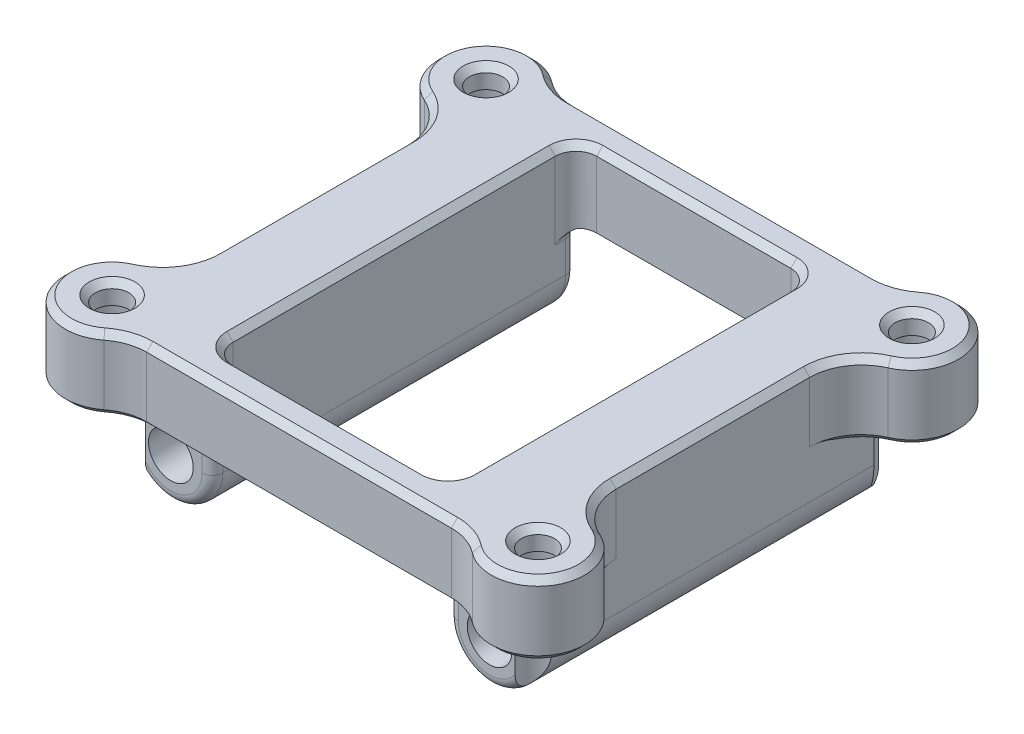
SolidWorks part; units mm, degrees
material "PLA"
ref_plane "正面" through (0, 0, 0) normal (0, 0, 1) x (1, 0, 0)
ref_plane "平面" through (0, 0, 0) normal (0, 1, 0) x (1, 0, 0)
ref_plane "右側面" through (0, 0, 0) normal (1, 0, 0) x (0, 0, -1)
sketch "ｽｹｯﾁ1" plane through (0, 0, 0) normal (0, 0, 1) x (1, 0, 0)
  line L0 (0, 0) -> (0, -9.0143) construction
  line L1 (0, 0) -> (35, 0) construction
  line L2 (0, 0) -> (15.343, 31.4578) construction
  line L3 (-7.343, 35.4578) -> (7.343, 35.4578)
  line L4 (-19.343, 31.4578) -> (-19.343, 35.4578)
  line L5 (-23.5, 42.4578) -> (23.5, 42.4578)
  line L6 (-23.5, 42.4578) -> (-23.5, 35.4578)
  line L7 (-23.5, 35.4578) -> (-23.343, 35.4578)
  line L8 (23.5, 42.4578) -> (23.5, 35.4578)
  line L9 (-23.5, 42.4578) -> (23.5, 35.4578) construction
  line L10 (-23.5, 35.4578) -> (23.5, 42.4578) construction
  line L11 (-15.343, 31.4578) -> (-15.343, 35.4578) construction
  line L12 (-23.343, 35.4578) -> (-15.343, 35.4578)
  line L13 (-7.343, 35.4578) -> (7.343, 35.4578)
  line L14 (-15.343, 35.4578) -> (-7.343, 35.4578)
  line L15 (-15.343, 35.4578) -> (-7.343, 35.4578) construction
  line L16 (7.343, 35.4578) -> (15.343, 35.4578)
  line L17 (23.343, 35.4578) -> (23.5, 35.4578)
  line L18 (7.343, 35.4578) -> (15.343, 35.4578) construction
  line L19 (15.343, 35.4578) -> (23.343, 35.4578)
  line L20 (-20.5, 42.4578) -> (-20.5, 35.4578) construction
  line L21 (20.5, 42.4578) -> (20.5, 35.4578) construction
  line L22 (-11.343, 31.4578) -> (-11.343, 35.4578)
  line L23 (11.343, 31.4578) -> (11.343, 35.4578)
  line L24 (19.343, 31.4578) -> (19.343, 35.4578)
  circle A2 centre (0, 0) radius 35 construction
  circle A4 centre (15.343, 31.4578) radius 2.15
  circle A5 centre (-15.343, 31.4578) radius 2.15
  arc A6 (11.6535, 33.003) -> (19.343, 31.4578) centre (15.343, 31.4578) ccw
  arc A7 (-11.6535, 33.003) -> (-19.343, 31.4578) centre (-15.343, 31.4578) cw
  arc A12 (-19.343, 31.4578) -> (-15.343, 35.4578) centre (-15.343, 31.4578) cw construction
  arc A13 (-15.343, 35.4578) -> (-11.6535, 33.003) centre (-15.343, 31.4578) cw construction
  arc A14 (15.343, 35.4578) -> (11.6535, 33.003) centre (15.343, 31.4578) ccw construction
  arc A15 (19.343, 31.4578) -> (15.343, 35.4578) centre (15.343, 31.4578) ccw construction
  point P15 (0, 38.9578)
  dimension "D1" = 70
  dimension "D2" = 64
  dimension "D3" = 4.3
  dimension "D4" = 8
  dimension "D5" = 47
  dimension "D6" = 7
  dimension "D7" = 41
extrude "ﾎﾞｽ - 押し出し1" add sketch "ｽｹｯﾁ1" along normal blind 42 contours L17 L8 L5 L6 L7 A7 L3 A6 A4 A5 | A7 L22 L14 L12 L4 A5 | L23 A6 L24 L19 L16 A4 region at (0, 38.9578, 0) region at (-11.4561, 33.4578, 0) region at (13.343, 35.3447, 0)
sketch "ｽｹｯﾁ2" plane through (0, 42.4578, 0) normal (0, 1, 0) x (1, 0, 0)
  line L0 (0, 0) -> (0, -42) construction
  line L1 (-23.5, -42) -> (23.5, -42) construction
  line L2 (0, -21) -> (20.5, -21) construction
  line L3 (-20.5, -3) -> (20.5, -3) construction
  line L4 (-20.5, -3) -> (-20.5, -39) construction
  line L5 (-20.5, -39) -> (20.5, -39) construction
  line L6 (20.5, -3) -> (20.5, -39) construction
  line L7 (-20.5, -3) -> (20.5, -39) construction
  line L8 (-20.5, -39) -> (20.5, -3) construction
  circle A0 centre (20.5, -3) radius 1.6
  circle A1 centre (-20.5, -3) radius 1.6
  circle A2 centre (20.5, -39) radius 1.6
  circle A3 centre (-20.5, -39) radius 1.6
  point P5 (0, -21)
  dimension "D3" = 3.2
  dimension "D1" = 41
  dimension "D2" = 36
extrude "ｶｯﾄ - 押し出し2" cut sketch "ｽｹｯﾁ2" against normal blind 7
sketch "ｽｹｯﾁ4" plane through (0, 0, 42) normal (0, 0, 1) x (1, 0, 0)
  line L0 (-19.343, 35.4578) -> (19.343, 35.4578)
  line L10 (-23.5, 35.4578) -> (-19.343, 35.4578)
  line L11 (-19.343, 35.4578) -> (-19.343, 31.4578)
  line L12 (-11.343, 31.4578) -> (-11.343, 35.4578)
  line L13 (-11.343, 35.4578) -> (11.343, 35.4578)
  line L14 (11.343, 35.4578) -> (11.343, 31.4578)
  line L15 (19.343, 31.4578) -> (19.343, 35.4578)
  line L16 (-23.5, 35.4578) -> (-19.343, 35.4578)
  line L17 (23.5, 35.4578) -> (23.5, 42.4578)
  line L18 (23.5, 42.4578) -> (-23.5, 42.4578)
  line L19 (-23.5, 42.4578) -> (-23.5, 35.4578)
  line L21 (-19.343, 35.4578) -> (-19.343, 31.4578)
  line L22 (-11.343, 31.4578) -> (-11.343, 35.4578)
  line L23 (-11.343, 35.4578) -> (11.343, 35.4578)
  line L24 (11.343, 35.4578) -> (11.343, 31.4578)
  line L25 (19.343, 31.4578) -> (19.343, 35.4578)
  line L27 (23.5, 35.4578) -> (23.5, 42.4578)
  line L28 (23.5, 42.4578) -> (-23.5, 42.4578)
  line L29 (-23.5, 42.4578) -> (-23.5, 35.4578)
  line L31 (19.343, 35.4578) -> (23.5, 35.4578)
  line L32 (19.343, 35.4578) -> (23.5, 35.4578)
  arc A2 (-19.343, 31.4578) -> (-11.343, 31.4578) centre (-15.343, 31.4578) ccw
  arc A3 (11.343, 31.4578) -> (19.343, 31.4578) centre (15.343, 31.4578) ccw
  arc A4 (-19.343, 31.4578) -> (-11.343, 31.4578) centre (-15.343, 31.4578) ccw
  arc A5 (11.343, 31.4578) -> (19.343, 31.4578) centre (15.343, 31.4578) ccw
  line M14 (-19.343, 35.4578) -> (-19.343, 31.4578)
  arc M15 (-19.343, 31.4578) -> (-11.343, 31.4578) centre (-15.343, 31.4578) ccw
  line M16 (-11.343, 31.4578) -> (-11.343, 35.4578)
  line M18 (11.343, 35.4578) -> (11.343, 31.4578)
  arc M19 (11.343, 31.4578) -> (19.343, 31.4578) centre (15.343, 31.4578) ccw
  line M20 (19.343, 31.4578) -> (19.343, 35.4578)
  circle M25 centre (15.343, 31.4578) radius 2.15
  circle M26 centre (-15.343, 31.4578) radius 2.15
  dimension "D1" = 0
extrude "ｶｯﾄ - 押し出し3" cut sketch "ｽｹｯﾁ4" against normal blind 3.5 contours L0 M18 M19 M20 M25 | L0 M14 M15 M16 M26 region at (-15.343, 35.3447, 42) region at (15.343, 35.3447, 42)
sketch "ｽｹｯﾁ5" plane through (0, 0, 0) normal (0, 0, -1) x (-1, 0, 0)
  line L0 (-19.343, 35.4578) -> (19.343, 35.4578)
  line L10 (19.343, 35.4578) -> (23.5, 35.4578)
  line L11 (23.5, 35.4578) -> (23.5, 42.4578)
  line L12 (23.5, 42.4578) -> (-23.5, 42.4578)
  line L13 (-23.5, 42.4578) -> (-23.5, 35.4578)
  line L14 (19.343, 35.4578) -> (23.5, 35.4578)
  line L15 (-19.343, 35.4578) -> (-19.343, 31.4578)
  line L16 (-11.343, 31.4578) -> (-11.343, 35.4578)
  line L17 (-23.5, 35.4578) -> (-19.343, 35.4578)
  line L18 (11.343, 35.4578) -> (11.343, 31.4578)
  line L19 (19.343, 31.4578) -> (19.343, 35.4578)
  line L21 (23.5, 35.4578) -> (23.5, 42.4578)
  line L22 (23.5, 42.4578) -> (-23.5, 42.4578)
  line L23 (-23.5, 42.4578) -> (-23.5, 35.4578)
  line L25 (-19.343, 35.4578) -> (-19.343, 31.4578)
  line L26 (-11.343, 31.4578) -> (-11.343, 35.4578)
  line L28 (11.343, 35.4578) -> (11.343, 31.4578)
  line L29 (19.343, 31.4578) -> (19.343, 35.4578)
  line L31 (-23.5, 35.4578) -> (-19.343, 35.4578)
  line L32 (-11.343, 35.4578) -> (11.343, 35.4578)
  line L33 (-11.343, 35.4578) -> (11.343, 35.4578)
  arc A2 (-19.343, 31.4578) -> (-11.343, 31.4578) centre (-15.343, 31.4578) ccw
  arc A3 (11.343, 31.4578) -> (19.343, 31.4578) centre (15.343, 31.4578) ccw
  arc A4 (-19.343, 31.4578) -> (-11.343, 31.4578) centre (-15.343, 31.4578) ccw
  arc A5 (11.343, 31.4578) -> (19.343, 31.4578) centre (15.343, 31.4578) ccw
  line M18 (-19.343, 35.4578) -> (-19.343, 31.4578)
  arc M19 (-19.343, 31.4578) -> (-11.343, 31.4578) centre (-15.343, 31.4578) ccw
  line M20 (-11.343, 31.4578) -> (-11.343, 35.4578)
  line M22 (11.343, 35.4578) -> (11.343, 31.4578)
  arc M23 (11.343, 31.4578) -> (19.343, 31.4578) centre (15.343, 31.4578) ccw
  line M24 (19.343, 31.4578) -> (19.343, 35.4578)
  circle M25 centre (-15.343, 31.4578) radius 2.15
  circle M26 centre (15.343, 31.4578) radius 2.15
  dimension "D1" = 0
extrude "ｶｯﾄ - 押し出し4" cut sketch "ｽｹｯﾁ5" against normal blind 3.5 contours L0 M22 M23 M24 M26 | L0 M18 M19 M20 M25 region at (15.343, 35.3447, 0) region at (-15.343, 35.3447, 0)
sketch "ｽｹｯﾁ7" plane through (0, 42.4578, 0) normal (0, 1, 0) x (1, 0, 0)
  line L0 (0, 0) -> (0, -42) construction
  line L1 (-23.5, -42) -> (23.5, -42) construction
  line L2 (23.5, -21) -> (0, -21) construction
  line L3 (23.5, -42) -> (23.5, 0) construction
  circle A0 centre (20.5, -3) radius 4.5
  circle A1 centre (20.5, -39) radius 4.5
  circle A2 centre (20.5, -39) radius 4.5
  circle A3 centre (20.5, -3) radius 4.5
  circle A4 centre (-20.5, -39) radius 4.5
  circle A5 centre (-20.5, -3) radius 4.5
  line M8 (23.5, 0) -> (-23.5, 0)
  line M9 (-23.5, 0) -> (-23.5, -42)
  line M10 (-23.5, -42) -> (23.5, -42)
  line M11 (23.5, -42) -> (23.5, 0)
  dimension "D1" = 9
extrude "ﾎﾞｽ - 押し出し2" add sketch "ｽｹｯﾁ7" against normal blind 7 contours A5 M9 M8 | A0 M11 M8 | A1 M11 M10 | A4 M9 M10 region at (24.5065, 42.4578, 4.7918) region at (-20.3229, 42.4578, -0.1111) region at (24.5065, 42.4578, 37.2082) region at (-23.6111, 42.4578, 38.8229)
sketch "ｽｹｯﾁ10" plane through (0, 35.4578, 0) normal (0, -1, 0) x (1, 0, 0)
  line L0 (0, 0) -> (0, 42) construction
  line L1 (-17.1459, 42) -> (17.1459, 42) construction
  line L2 (0, 21) -> (23.5, 21) construction
  line L3 (23.5, 35.6459) -> (23.5, 6.3541) construction
  circle A0 centre (20.5, 39) radius 2.6
  circle A1 centre (20.5, 3) radius 2.6
  circle A2 centre (-20.5, 39) radius 2.6
  circle A3 centre (-20.5, 3) radius 2.6
  dimension "D1" = 5.2
extrude "ｶｯﾄ - 押し出し7" cut sketch "ｽｹｯﾁ10" against normal blind 5
sketch "ｽｹｯﾁ8" plane through (0, 35.4578, 0) normal (0, -1, 0) x (1, 0, 0)
  line L0 (19.5566, 41.5) -> (19.0566, 41.5) construction
  line L1 (22.1934, 36.933) -> (23.1368, 38.567)
  line L2 (23.1368, 39.433) -> (22.1934, 41.067)
  line L3 (21.4434, 41.5) -> (19.5566, 41.5)
  line L4 (18.8066, 41.067) -> (17.8632, 39.433)
  line L5 (17.8632, 38.567) -> (18.8066, 36.933)
  line L6 (19.5566, 36.5) -> (21.4434, 36.5)
  line L7 (19.0566, 41.5) -> (18.8066, 41.067) construction
  line L8 (21.9434, 41.5) -> (21.4434, 41.5) construction
  line L9 (22.1934, 41.067) -> (21.9434, 41.5) construction
  line L10 (23.3868, 39) -> (23.1368, 39.433) construction
  line L11 (23.1368, 38.567) -> (23.3868, 39) construction
  line L12 (21.9434, 36.5) -> (22.1934, 36.933) construction
  line L13 (21.4434, 36.5) -> (21.9434, 36.5) construction
  line L14 (18.8066, 36.933) -> (19.0566, 36.5) construction
  line L15 (19.0566, 36.5) -> (19.5566, 36.5) construction
  line L16 (17.8632, 39.433) -> (17.6132, 39) construction
  line L17 (17.6132, 39) -> (17.8632, 38.567) construction
  line L18 (0, 0) -> (0, 42) construction
  line L19 (-17.1459, 42) -> (17.1459, 42) construction
  line L20 (0, 21) -> (23.5, 21) construction
  line L21 (23.5, 35.6459) -> (23.5, 6.3541) construction
  line L22 (-17.6132, 39) -> (-17.8632, 38.567) construction
  line L23 (-17.8632, 39.433) -> (-17.6132, 39) construction
  line L24 (-19.0566, 36.5) -> (-19.5566, 36.5) construction
  line L25 (-18.8066, 36.933) -> (-19.0566, 36.5) construction
  line L26 (-21.4434, 36.5) -> (-21.9434, 36.5) construction
  line L27 (-21.9434, 36.5) -> (-22.1934, 36.933) construction
  line L28 (-22.1934, 41.067) -> (-21.9434, 41.5) construction
  line L29 (-21.9434, 41.5) -> (-21.4434, 41.5) construction
  line L30 (-19.0566, 41.5) -> (-18.8066, 41.067) construction
  line L31 (-19.5566, 41.5) -> (-19.0566, 41.5) construction
  line L32 (-19.5566, 36.5) -> (-21.4434, 36.5)
  line L33 (-17.8632, 38.567) -> (-18.8066, 36.933)
  line L34 (-18.8066, 41.067) -> (-17.8632, 39.433)
  line L35 (-21.4434, 41.5) -> (-19.5566, 41.5)
  line L36 (-23.1368, 39.433) -> (-22.1934, 41.067)
  line L37 (-22.1934, 36.933) -> (-23.1368, 38.567)
  line L38 (17.6132, 3) -> (17.8632, 3.433) construction
  line L39 (17.8632, 2.567) -> (17.6132, 3) construction
  line L40 (19.0566, 5.5) -> (19.5566, 5.5) construction
  line L41 (18.8066, 5.067) -> (19.0566, 5.5) construction
  line L42 (21.4434, 5.5) -> (21.9434, 5.5) construction
  line L43 (21.9434, 5.5) -> (22.1934, 5.067) construction
  line L44 (23.1368, 3.433) -> (23.3868, 3) construction
  line L45 (23.3868, 3) -> (23.1368, 2.567) construction
  line L46 (22.1934, 0.933) -> (21.9434, 0.5) construction
  line L47 (21.9434, 0.5) -> (21.4434, 0.5) construction
  line L48 (19.0566, 0.5) -> (18.8066, 0.933) construction
  line L49 (19.5566, 0.5) -> (19.0566, 0.5) construction
  line L50 (19.5566, 5.5) -> (21.4434, 5.5)
  line L51 (17.8632, 3.433) -> (18.8066, 5.067)
  line L52 (18.8066, 0.933) -> (17.8632, 2.567)
  line L53 (21.4434, 0.5) -> (19.5566, 0.5)
  line L54 (23.1368, 2.567) -> (22.1934, 0.933)
  line L55 (22.1934, 5.067) -> (23.1368, 3.433)
  line L56 (-19.5566, 0.5) -> (-19.0566, 0.5) construction
  line L57 (-19.0566, 0.5) -> (-18.8066, 0.933) construction
  line L58 (-21.9434, 0.5) -> (-21.4434, 0.5) construction
  line L59 (-22.1934, 0.933) -> (-21.9434, 0.5) construction
  line L60 (-23.3868, 3) -> (-23.1368, 2.567) construction
  line L61 (-23.1368, 3.433) -> (-23.3868, 3) construction
  line L62 (-21.9434, 5.5) -> (-22.1934, 5.067) construction
  line L63 (-21.4434, 5.5) -> (-21.9434, 5.5) construction
  line L64 (-18.8066, 5.067) -> (-19.0566, 5.5) construction
  line L65 (-19.0566, 5.5) -> (-19.5566, 5.5) construction
  line L66 (-17.8632, 2.567) -> (-17.6132, 3) construction
  line L67 (-17.6132, 3) -> (-17.8632, 3.433) construction
  line L68 (-22.1934, 5.067) -> (-23.1368, 3.433)
  line L69 (-23.1368, 2.567) -> (-22.1934, 0.933)
  line L70 (-21.4434, 0.5) -> (-19.5566, 0.5)
  line L71 (-18.8066, 0.933) -> (-17.8632, 2.567)
  line L72 (-17.8632, 3.433) -> (-18.8066, 5.067)
  line L73 (-19.5566, 5.5) -> (-21.4434, 5.5)
  arc A0 (22.9826, 39.2944) -> (18.0174, 39.2944) centre (20.5, 39) ccw construction
  arc A1 (21.4864, 41.2972) -> (21.9963, 41.0028) centre (21.9434, 41.5) ccw construction
  arc A2 (23.1368, 38.567) -> (23.1368, 39.433) centre (23.3868, 39) ccw
  arc A3 (21.4434, 36.5) -> (22.1934, 36.933) centre (21.9434, 36.5) ccw
  arc A4 (18.8066, 36.933) -> (19.5566, 36.5) centre (19.0566, 36.5) ccw
  arc A5 (17.8632, 39.433) -> (17.8632, 38.567) centre (17.6132, 39) ccw
  arc A6 (19.5566, 41.5) -> (18.8066, 41.067) centre (19.0566, 41.5) ccw
  arc A7 (18.8066, 41.067) -> (19.0037, 41.0028) centre (19.0566, 41.5) ccw construction
  arc A8 (19.0037, 41.0028) -> (19.5136, 41.2972) centre (19.0566, 41.5) ccw construction
  arc A9 (19.5136, 41.2972) -> (19.5566, 41.5) centre (19.0566, 41.5) ccw construction
  arc A10 (21.4434, 41.5) -> (21.4864, 41.2972) centre (21.9434, 41.5) ccw construction
  arc A11 (21.9963, 41.0028) -> (22.1934, 41.067) centre (21.9434, 41.5) ccw construction
  arc A12 (22.1934, 41.067) -> (21.4434, 41.5) centre (21.9434, 41.5) ccw
  arc A13 (23.1368, 39.433) -> (22.9826, 39.2944) centre (23.3868, 39) ccw construction
  arc A14 (22.9826, 38.7056) -> (22.9826, 39.2944) centre (20.5, 39) ccw construction
  arc A15 (22.9826, 39.2944) -> (22.9826, 38.7056) centre (23.3868, 39) ccw construction
  arc A16 (22.9826, 38.7056) -> (23.1368, 38.567) centre (23.3868, 39) ccw construction
  arc A17 (22.1934, 36.933) -> (21.9963, 36.9972) centre (21.9434, 36.5) ccw construction
  arc A18 (21.9963, 36.9972) -> (22.6651, 37.75) centre (20.5, 39) ccw construction
  arc A19 (22.6651, 37.75) -> (22.9826, 38.7056) centre (20.5, 39) ccw construction
  arc A20 (21.9963, 36.9972) -> (21.4864, 36.7028) centre (21.9434, 36.5) ccw construction
  arc A21 (21.4864, 36.7028) -> (21.9963, 36.9972) centre (20.5, 39) ccw construction
  arc A22 (21.4864, 36.7028) -> (21.4434, 36.5) centre (21.9434, 36.5) ccw construction
  arc A23 (19.0037, 36.9972) -> (18.8066, 36.933) centre (19.0566, 36.5) ccw construction
  arc A24 (18.3349, 37.75) -> (19.0037, 36.9972) centre (20.5, 39) ccw construction
  arc A25 (19.5136, 36.7028) -> (21.4864, 36.7028) centre (20.5, 39) ccw construction
  arc A26 (19.5136, 36.7028) -> (19.0037, 36.9972) centre (19.0566, 36.5) ccw construction
  arc A27 (19.0037, 36.9972) -> (19.5136, 36.7028) centre (20.5, 39) ccw construction
  arc A28 (19.5566, 36.5) -> (19.5136, 36.7028) centre (19.0566, 36.5) ccw construction
  arc A29 (18.0174, 39.2944) -> (18.0174, 38.7056) centre (20.5, 39) ccw construction
  arc A30 (18.0174, 38.7056) -> (18.3349, 37.75) centre (20.5, 39) ccw construction
  arc A31 (18.0174, 38.7056) -> (18.0174, 39.2944) centre (17.6132, 39) ccw construction
  arc A32 (18.0174, 39.2944) -> (17.8632, 39.433) centre (17.6132, 39) ccw construction
  arc A33 (17.8632, 38.567) -> (18.0174, 38.7056) centre (17.6132, 39) ccw construction
  arc A34 (-23.1368, 38.567) -> (-23.1368, 39.433) centre (-23.3868, 39) cw
  arc A35 (-17.8632, 38.567) -> (-18.0174, 38.7056) centre (-17.6132, 39) cw construction
  arc A36 (-18.0174, 39.2944) -> (-17.8632, 39.433) centre (-17.6132, 39) cw construction
  arc A37 (-18.0174, 38.7056) -> (-18.0174, 39.2944) centre (-17.6132, 39) cw construction
  arc A38 (-18.0174, 38.7056) -> (-18.3349, 37.75) centre (-20.5, 39) cw construction
  arc A39 (-18.0174, 39.2944) -> (-18.0174, 38.7056) centre (-20.5, 39) cw construction
  arc A40 (-19.5566, 36.5) -> (-19.5136, 36.7028) centre (-19.0566, 36.5) cw construction
  arc A41 (-19.0037, 36.9972) -> (-19.5136, 36.7028) centre (-20.5, 39) cw construction
  arc A42 (-19.5136, 36.7028) -> (-19.0037, 36.9972) centre (-19.0566, 36.5) cw construction
  arc A43 (-19.5136, 36.7028) -> (-21.4864, 36.7028) centre (-20.5, 39) cw construction
  arc A44 (-18.3349, 37.75) -> (-19.0037, 36.9972) centre (-20.5, 39) cw construction
  arc A45 (-19.0037, 36.9972) -> (-18.8066, 36.933) centre (-19.0566, 36.5) cw construction
  arc A46 (-21.4864, 36.7028) -> (-21.4434, 36.5) centre (-21.9434, 36.5) cw construction
  arc A47 (-21.4864, 36.7028) -> (-21.9963, 36.9972) centre (-20.5, 39) cw construction
  arc A48 (-21.9963, 36.9972) -> (-21.4864, 36.7028) centre (-21.9434, 36.5) cw construction
  arc A49 (-22.6651, 37.75) -> (-22.9826, 38.7056) centre (-20.5, 39) cw construction
  arc A50 (-21.9963, 36.9972) -> (-22.6651, 37.75) centre (-20.5, 39) cw construction
  arc A51 (-22.1934, 36.933) -> (-21.9963, 36.9972) centre (-21.9434, 36.5) cw construction
  arc A52 (-22.9826, 38.7056) -> (-23.1368, 38.567) centre (-23.3868, 39) cw construction
  arc A53 (-22.9826, 39.2944) -> (-22.9826, 38.7056) centre (-23.3868, 39) cw construction
  arc A54 (-22.9826, 38.7056) -> (-22.9826, 39.2944) centre (-20.5, 39) cw construction
  arc A55 (-23.1368, 39.433) -> (-22.9826, 39.2944) centre (-23.3868, 39) cw construction
  arc A56 (-21.9963, 41.0028) -> (-22.1934, 41.067) centre (-21.9434, 41.5) cw construction
  arc A57 (-21.4434, 41.5) -> (-21.4864, 41.2972) centre (-21.9434, 41.5) cw construction
  arc A58 (-19.5136, 41.2972) -> (-19.5566, 41.5) centre (-19.0566, 41.5) cw construction
  arc A59 (-19.0037, 41.0028) -> (-19.5136, 41.2972) centre (-19.0566, 41.5) cw construction
  arc A60 (-18.8066, 41.067) -> (-19.0037, 41.0028) centre (-19.0566, 41.5) cw construction
  arc A61 (-21.4864, 41.2972) -> (-21.9963, 41.0028) centre (-21.9434, 41.5) cw construction
  arc A62 (-22.9826, 39.2944) -> (-18.0174, 39.2944) centre (-20.5, 39) cw construction
  arc A63 (-22.1934, 41.067) -> (-21.4434, 41.5) centre (-21.9434, 41.5) cw
  arc A64 (-19.5566, 41.5) -> (-18.8066, 41.067) centre (-19.0566, 41.5) cw
  arc A65 (-17.8632, 39.433) -> (-17.8632, 38.567) centre (-17.6132, 39) cw
  arc A66 (-18.8066, 36.933) -> (-19.5566, 36.5) centre (-19.0566, 36.5) cw
  arc A67 (-21.4434, 36.5) -> (-22.1934, 36.933) centre (-21.9434, 36.5) cw
  arc A68 (23.1368, 3.433) -> (23.1368, 2.567) centre (23.3868, 3) cw
  arc A69 (17.8632, 3.433) -> (18.0174, 3.2944) centre (17.6132, 3) cw construction
  arc A70 (18.0174, 2.7056) -> (17.8632, 2.567) centre (17.6132, 3) cw construction
  arc A71 (18.0174, 3.2944) -> (18.0174, 2.7056) centre (17.6132, 3) cw construction
  arc A72 (18.0174, 3.2944) -> (18.3349, 4.25) centre (20.5, 3) cw construction
  arc A73 (18.0174, 2.7056) -> (18.0174, 3.2944) centre (20.5, 3) cw construction
  arc A74 (19.5566, 5.5) -> (19.5136, 5.2972) centre (19.0566, 5.5) cw construction
  arc A75 (19.0037, 5.0028) -> (19.5136, 5.2972) centre (20.5, 3) cw construction
  arc A76 (19.5136, 5.2972) -> (19.0037, 5.0028) centre (19.0566, 5.5) cw construction
  arc A77 (19.5136, 5.2972) -> (21.4864, 5.2972) centre (20.5, 3) cw construction
  arc A78 (18.3349, 4.25) -> (19.0037, 5.0028) centre (20.5, 3) cw construction
  arc A79 (19.0037, 5.0028) -> (18.8066, 5.067) centre (19.0566, 5.5) cw construction
  arc A80 (21.4864, 5.2972) -> (21.4434, 5.5) centre (21.9434, 5.5) cw construction
  arc A81 (21.4864, 5.2972) -> (21.9963, 5.0028) centre (20.5, 3) cw construction
  arc A82 (21.9963, 5.0028) -> (21.4864, 5.2972) centre (21.9434, 5.5) cw construction
  arc A83 (22.6651, 4.25) -> (22.9826, 3.2944) centre (20.5, 3) cw construction
  arc A84 (21.9963, 5.0028) -> (22.6651, 4.25) centre (20.5, 3) cw construction
  arc A85 (22.1934, 5.067) -> (21.9963, 5.0028) centre (21.9434, 5.5) cw construction
  arc A86 (22.9826, 3.2944) -> (23.1368, 3.433) centre (23.3868, 3) cw construction
  arc A87 (22.9826, 2.7056) -> (22.9826, 3.2944) centre (23.3868, 3) cw construction
  arc A88 (22.9826, 3.2944) -> (22.9826, 2.7056) centre (20.5, 3) cw construction
  arc A89 (23.1368, 2.567) -> (22.9826, 2.7056) centre (23.3868, 3) cw construction
  arc A90 (21.9963, 0.9972) -> (22.1934, 0.933) centre (21.9434, 0.5) cw construction
  arc A91 (21.4434, 0.5) -> (21.4864, 0.7028) centre (21.9434, 0.5) cw construction
  arc A92 (19.5136, 0.7028) -> (19.5566, 0.5) centre (19.0566, 0.5) cw construction
  arc A93 (19.0037, 0.9972) -> (19.5136, 0.7028) centre (19.0566, 0.5) cw construction
  arc A94 (18.8066, 0.933) -> (19.0037, 0.9972) centre (19.0566, 0.5) cw construction
  arc A95 (21.4864, 0.7028) -> (21.9963, 0.9972) centre (21.9434, 0.5) cw construction
  arc A96 (22.9826, 2.7056) -> (18.0174, 2.7056) centre (20.5, 3) cw construction
  arc A97 (22.1934, 0.933) -> (21.4434, 0.5) centre (21.9434, 0.5) cw
  arc A98 (19.5566, 0.5) -> (18.8066, 0.933) centre (19.0566, 0.5) cw
  arc A99 (17.8632, 2.567) -> (17.8632, 3.433) centre (17.6132, 3) cw
  arc A100 (18.8066, 5.067) -> (19.5566, 5.5) centre (19.0566, 5.5) cw
  arc A101 (21.4434, 5.5) -> (22.1934, 5.067) centre (21.9434, 5.5) cw
  arc A102 (-22.9826, 2.7056) -> (-18.0174, 2.7056) centre (-20.5, 3) ccw construction
  arc A103 (-21.4864, 0.7028) -> (-21.9963, 0.9972) centre (-21.9434, 0.5) ccw construction
  arc A104 (-18.8066, 0.933) -> (-19.0037, 0.9972) centre (-19.0566, 0.5) ccw construction
  arc A105 (-19.0037, 0.9972) -> (-19.5136, 0.7028) centre (-19.0566, 0.5) ccw construction
  arc A106 (-19.5136, 0.7028) -> (-19.5566, 0.5) centre (-19.0566, 0.5) ccw construction
  arc A107 (-21.4434, 0.5) -> (-21.4864, 0.7028) centre (-21.9434, 0.5) ccw construction
  arc A108 (-21.9963, 0.9972) -> (-22.1934, 0.933) centre (-21.9434, 0.5) ccw construction
  arc A109 (-23.1368, 2.567) -> (-22.9826, 2.7056) centre (-23.3868, 3) ccw construction
  arc A110 (-22.9826, 3.2944) -> (-22.9826, 2.7056) centre (-20.5, 3) ccw construction
  arc A111 (-22.9826, 2.7056) -> (-22.9826, 3.2944) centre (-23.3868, 3) ccw construction
  arc A112 (-22.9826, 3.2944) -> (-23.1368, 3.433) centre (-23.3868, 3) ccw construction
  arc A113 (-22.1934, 5.067) -> (-21.9963, 5.0028) centre (-21.9434, 5.5) ccw construction
  arc A114 (-21.9963, 5.0028) -> (-22.6651, 4.25) centre (-20.5, 3) ccw construction
  arc A115 (-22.6651, 4.25) -> (-22.9826, 3.2944) centre (-20.5, 3) ccw construction
  arc A116 (-21.9963, 5.0028) -> (-21.4864, 5.2972) centre (-21.9434, 5.5) ccw construction
  arc A117 (-21.4864, 5.2972) -> (-21.9963, 5.0028) centre (-20.5, 3) ccw construction
  arc A118 (-21.4864, 5.2972) -> (-21.4434, 5.5) centre (-21.9434, 5.5) ccw construction
  arc A119 (-19.0037, 5.0028) -> (-18.8066, 5.067) centre (-19.0566, 5.5) ccw construction
  arc A120 (-18.3349, 4.25) -> (-19.0037, 5.0028) centre (-20.5, 3) ccw construction
  arc A121 (-19.5136, 5.2972) -> (-21.4864, 5.2972) centre (-20.5, 3) ccw construction
  arc A122 (-19.5136, 5.2972) -> (-19.0037, 5.0028) centre (-19.0566, 5.5) ccw construction
  arc A123 (-19.0037, 5.0028) -> (-19.5136, 5.2972) centre (-20.5, 3) ccw construction
  arc A124 (-19.5566, 5.5) -> (-19.5136, 5.2972) centre (-19.0566, 5.5) ccw construction
  arc A125 (-18.0174, 2.7056) -> (-18.0174, 3.2944) centre (-20.5, 3) ccw construction
  arc A126 (-18.0174, 3.2944) -> (-18.3349, 4.25) centre (-20.5, 3) ccw construction
  arc A127 (-18.0174, 3.2944) -> (-18.0174, 2.7056) centre (-17.6132, 3) ccw construction
  arc A128 (-18.0174, 2.7056) -> (-17.8632, 2.567) centre (-17.6132, 3) ccw construction
  arc A129 (-17.8632, 3.433) -> (-18.0174, 3.2944) centre (-17.6132, 3) ccw construction
  arc A130 (-21.4434, 5.5) -> (-22.1934, 5.067) centre (-21.9434, 5.5) ccw
  arc A131 (-18.8066, 5.067) -> (-19.5566, 5.5) centre (-19.0566, 5.5) ccw
  arc A132 (-17.8632, 2.567) -> (-17.8632, 3.433) centre (-17.6132, 3) ccw
  arc A133 (-19.5566, 0.5) -> (-18.8066, 0.933) centre (-19.0566, 0.5) ccw
  arc A134 (-22.1934, 0.933) -> (-21.4434, 0.5) centre (-21.9434, 0.5) ccw
  arc A135 (-23.1368, 3.433) -> (-23.1368, 2.567) centre (-23.3868, 3) ccw
  dimension "D2" = 1
  dimension "D1" = 5
  dimension "D3" = 6
extrude "ｶｯﾄ - 押し出し5" [suppressed] cut sketch "ｽｹｯﾁ8" against normal blind 3
sketch "ｽｹｯﾁ11" plane through (0, 35.4578, 0) normal (0, -1, 0) x (1, 0, 0)
  line L0 (0, 42) -> (0, 0) construction
  line L1 (-17.1459, 42) -> (17.1459, 42) construction
  line L2 (0, 21) -> (23.5, 21) construction
  line L3 (23.5, 35.6459) -> (23.5, 6.3541) construction
  circle A0 centre (20.5, 39) radius 2.75
  circle A1 centre (20.5, 3) radius 2.75
  circle A2 centre (-20.5, 39) radius 2.75
  circle A3 centre (-20.5, 3) radius 2.75
  dimension "D1" = 5.5
extrude "ｶｯﾄ - 押し出し8" cut sketch "ｽｹｯﾁ11" along normal through all
sketch "ｽｹｯﾁ12" plane through (0, 42.4578, 0) normal (0, 1, 0) x (1, 0, 0)
  line L0 (0, 0) -> (0, -42) construction
  line L1 (-17.1459, -42) -> (17.1459, -42) construction
  line L2 (0, -21) -> (23.5, -21) construction
  line L3 (-16.7583, -0.5) -> (16.7583, -0.5)
  line L4 (-17.1459, -0.5) -> (-17.1459, 0) construction
  line L5 (-17.1459, 0) -> (17.1459, 0)
  line L6 (17.1459, -0.5) -> (17.1459, 0) construction
  line L7 (-16.7621, -0.4944) -> (17.1459, 0) construction
  line L8 (-17.1459, 0) -> (16.7621, -0.4944) construction
  line L9 (23.5, -35.6459) -> (23.5, -6.3541) construction
  line L10 (-17.1459, -42) -> (16.7621, -41.5056) construction
  line L11 (-16.7621, -41.5056) -> (17.1459, -42) construction
  line L12 (17.1459, -41.5) -> (17.1459, -42) construction
  line L13 (-17.1459, -42) -> (17.1459, -42)
  line L14 (-17.1459, -41.5) -> (-17.1459, -42) construction
  line L15 (-16.7583, -41.5) -> (16.7583, -41.5)
  line L16 (16.7621, -0.4944) -> (17.1459, -0.5) construction
  line L17 (16.7583, -0.5) -> (17.1459, -0.5) construction
  line L18 (23.5, -21) -> (23.5, -6.3541) construction
  line L19 (16.7621, -41.5056) -> (17.1459, -41.5) construction
  line L20 (-23.5, -6.3541) -> (-23.5, -35.6459)
  line L21 (-23.5, -6.3541) -> (-23.5, -35.6459)
  line L22 (-17.1459, -42) -> (17.1459, -42)
  line L23 (-17.1459, -42) -> (17.1459, -42)
  line L24 (23.5, -35.6459) -> (23.5, -6.3541)
  line L25 (23.5, -35.6459) -> (23.5, -6.3541)
  line L26 (17.1459, 0) -> (-17.1459, 0)
  line L27 (17.1459, 0) -> (-17.1459, 0)
  line L28 (16.7583, -41.5) -> (17.1459, -41.5) construction
  line L29 (-17.1459, -41.5) -> (-16.7583, -41.5) construction
  line L30 (-17.1459, -41.5) -> (-16.7621, -41.5056) construction
  line L31 (-17.1459, -0.5) -> (-16.7621, -0.4944) construction
  line L32 (-17.1459, -0.5) -> (-16.7583, -0.5) construction
  arc A0 (17.1459, 0) -> (16.7583, -0.5) centre (20.5, -3) ccw
  arc A1 (17.1459, -42) -> (16.7583, -41.5) centre (20.5, -39) cw
  arc A2 (-17.1459, -42) -> (-16.7583, -41.5) centre (-20.5, -39) ccw
  arc A3 (-17.1459, 0) -> (-16.7583, -0.5) centre (-20.5, -3) cw
  arc A4 (-23.5, -35.6459) -> (-17.1459, -42) centre (-20.5, -39) ccw
  arc A5 (17.1459, -42) -> (23.5, -35.6459) centre (20.5, -39) ccw
  arc A6 (23.5, -6.3541) -> (17.1459, 0) centre (20.5, -3) ccw
  arc A7 (-17.1459, 0) -> (-23.5, -6.3541) centre (-20.5, -3) ccw
  arc A8 (-23.5, -35.6459) -> (-17.1459, -42) centre (-20.5, -39) ccw construction
  arc A9 (17.1459, -42) -> (23.5, -35.6459) centre (20.5, -39) ccw construction
  arc A10 (23.5, -6.3541) -> (17.1459, 0) centre (20.5, -3) ccw construction
  arc A11 (-17.1459, 0) -> (-23.5, -6.3541) centre (-20.5, -3) ccw construction
  arc A12 (16.7583, -0.5) -> (23.5, -6.3541) centre (20.5, -3) ccw construction
  arc A13 (23.5, -6.3541) -> (17.1459, 0) centre (20.5, -3) ccw construction
  arc A14 (16.7583, -41.5) -> (23.5, -35.6459) centre (20.5, -39) cw construction
  arc A15 (23.5, -35.6459) -> (17.1459, -42) centre (20.5, -39) cw construction
  arc A16 (-16.7583, -41.5) -> (-23.5, -35.6459) centre (-20.5, -39) ccw construction
  arc A17 (-23.5, -35.6459) -> (-17.1459, -42) centre (-20.5, -39) ccw construction
  arc A18 (-16.7583, -0.5) -> (-23.5, -6.3541) centre (-20.5, -3) cw construction
  arc A19 (-23.5, -6.3541) -> (-17.1459, 0) centre (-20.5, -3) cw construction
  point P5 (0, -0.25)
  point P19 (0, -41.75)
  line M9 (-17.1459, -42) -> (17.1459, -42)
  line M13 (17.1459, 0) -> (-17.1459, 0)
  dimension "D1" = 41
  dimension "D2" = 0
extrude "ｶｯﾄ - 押し出し9" cut sketch "ｽｹｯﾁ12" against normal through all contours A2 A1 L15 M9 | A3 L3 A0 M13 region at (0, 42.4578, 0.249) region at (0, 42.4578, 41.751)
sketch "ｽｹｯﾁ14" plane through (0, 35.4578, 0) normal (0, -1, 0) x (1, 0, 0)
  line L0 (0, 0.5) -> (0, 41.5) construction
  line L1 (-16.7583, 0.5) -> (16.7583, 0.5) construction
  line L2 (-16.7583, 41.5) -> (16.7583, 41.5) construction
  line L4 (11.343, 3.5) -> (-11.343, 3.5)
  line L5 (11.343, 3.5) -> (11.343, 38.5)
  line L6 (11.343, 38.5) -> (-11.343, 38.5)
  line L7 (19.343, 5.4948) -> (19.343, 36.5052)
  line L8 (11.343, 3.5) -> (17.7958, 3.5)
  line L9 (11.343, 38.5) -> (11.343, 3.5)
  line L10 (17.7958, 38.5) -> (11.343, 38.5)
  line L11 (19.343, 5.4948) -> (19.343, 36.5052)
  line L12 (11.343, 3.5) -> (17.7958, 3.5)
  line L13 (11.343, 38.5) -> (11.343, 3.5)
  line L14 (17.7958, 38.5) -> (11.343, 38.5)
  line L15 (-19.343, 36.5052) -> (-19.343, 5.4948)
  line L16 (-11.343, 38.5) -> (-17.7958, 38.5)
  line L17 (-11.343, 3.5) -> (-11.343, 38.5)
  line L18 (-17.7958, 3.5) -> (-11.343, 3.5)
  line L19 (-19.343, 36.5052) -> (-19.343, 5.4948)
  line L20 (-11.343, 38.5) -> (-17.7958, 38.5)
  line L21 (-11.343, 3.5) -> (-11.343, 38.5)
  line L22 (-17.7958, 3.5) -> (-11.343, 3.5)
  line L23 (-11.343, 3.5) -> (-11.343, 38.5)
  line L24 (11.343, 3.5) -> (-11.343, 38.5) construction
  line L25 (11.343, 38.5) -> (-11.343, 3.5) construction
  line L29 (16.7583, 41.5) -> (-16.7583, 41.5)
  line L30 (-23.5, 35.6459) -> (-23.5, 6.3541)
  line L31 (-16.7583, 0.5) -> (16.7583, 0.5)
  line L32 (-23.5, 35.6459) -> (-23.5, 6.3541)
  line L33 (16.7583, 41.5) -> (-16.7583, 41.5)
  line L35 (-16.7583, 0.5) -> (16.7583, 0.5)
  line L37 (23.5, 6.3541) -> (23.5, 35.6459)
  line L38 (23.5, 6.3541) -> (23.5, 35.6459)
  circle A0 centre (20.5, 39) radius 4.5
  circle A1 centre (20.5, 3) radius 4.5
  arc A2 (17.7958, 38.5) -> (19.343, 36.5052) centre (20.5, 39) ccw
  arc A3 (17.7958, 38.5) -> (19.343, 36.5052) centre (20.5, 39) ccw
  arc A6 (-19.343, 36.5052) -> (-17.7958, 38.5) centre (-20.5, 39) ccw
  arc A7 (-19.343, 36.5052) -> (-17.7958, 38.5) centre (-20.5, 39) ccw
  circle A10 centre (-20.5, 3) radius 4.5
  circle A11 centre (-20.5, 39) radius 4.5
  arc A14 (19.343, 5.4948) -> (17.7958, 3.5) centre (20.5, 3) ccw
  arc A15 (19.343, 5.4948) -> (17.7958, 3.5) centre (20.5, 3) ccw
  arc A16 (-16.7583, 41.5) -> (-23.5, 35.6459) centre (-20.5, 39) ccw
  arc A17 (-23.5, 6.3541) -> (-16.7583, 0.5) centre (-20.5, 3) ccw
  arc A18 (16.7583, 0.5) -> (23.5, 6.3541) centre (20.5, 3) ccw
  arc A19 (23.5, 35.6459) -> (16.7583, 41.5) centre (20.5, 39) ccw
  arc A20 (-16.7583, 41.5) -> (-23.5, 35.6459) centre (-20.5, 39) ccw
  arc A21 (-23.5, 6.3541) -> (-16.7583, 0.5) centre (-20.5, 3) ccw
  arc A22 (16.7583, 0.5) -> (23.5, 6.3541) centre (20.5, 3) ccw
  arc A23 (23.5, 35.6459) -> (16.7583, 41.5) centre (20.5, 39) ccw
  arc A24 (-17.7958, 3.5) -> (-19.343, 5.4948) centre (-20.5, 3) ccw
  arc A25 (-17.7958, 3.5) -> (-19.343, 5.4948) centre (-20.5, 3) ccw
  point P15 (0, 21)
  line M15 (-23.5, 35.6459) -> (-23.5, 6.3541)
  line M19 (23.5, 6.3541) -> (23.5, 35.6459)
  line M24 (-11.343, 38.5) -> (-11.343, 3.5)
  line M30 (11.343, 3.5) -> (11.343, 38.5)
  dimension "D1" = 0
  dimension "D2" = 0
  dimension "D3" = 0
extrude "ｶｯﾄ - 押し出し11" cut sketch "ｽｹｯﾁ14" against normal through all contours L6 L4 M30 M24 | A11 A10 L19 M15 | A1 A0 L11 M19 region at (0, 35.4578, 21) region at (21.4451, 35.4578, 21) region at (-21.4451, 35.4578, 21)
fillet "ﾌｨﾚｯﾄ1" radius 5 8 edges at (19.343, 38.9578, 7.3487) (16.7583, 38.9578, 0.5) (-16.7583, 38.9578, 0.5) (-19.343, 38.9578, 7.3487) (-19.343, 38.9578, 34.6513) (-16.7583, 38.9578, 41.5) (19.343, 38.9578, 34.6513) (16.7583, 38.9578, 41.5)
fillet "ﾌｨﾚｯﾄ2" radius 2 4 edges at (11.343, 38.9578, 38.5) (11.343, 38.9578, 3.5) (-11.343, 38.9578, 3.5) (-11.343, 38.9578, 38.5)
chamfer "面取り1" distance 0.6 angle 45 42 edges at (16.2913, 42.4578, 0.2295) (0, 42.4578, 0.5) (24.3628, 42.4578, 0.6916) (-16.2913, 42.4578, 0.2295) (20.1529, 42.4578, 8.9597) (-24.3628, 42.4578, 0.6916) (19.343, 42.4578, 21) (-20.1529, 42.4578, 8.9597) (20.1529, 42.4578, 33.0403) (24.3628, 42.4578, 41.3084) (-20.1529, 42.4578, 33.0403) (16.2913, 42.4578, 41.7705) (-24.3628, 42.4578, 41.3084) (0, 42.4578, 41.5) (-16.2913, 42.4578, 41.7705) (11.343, 42.4578, 21) (10.7572, 42.4578, 4.0858) (10.7572, 42.4578, 37.9142) (-10.7572, 42.4578, 4.0858) (-10.7572, 42.4578, 37.9142) (-11.343, 42.4578, 21) (0, 42.4578, 38.5) (0, 42.4578, 3.5) (-19.343, 42.4578, 21) (20.1529, 35.4578, 33.0403) (24.3628, 35.4578, 41.3084) (16.2913, 35.4578, 41.7705) (-20.1529, 35.4578, 33.0403) (0, 35.4578, 41.5) (-24.3628, 35.4578, 41.3084) (-16.2913, 35.4578, 41.7705) (-20.1529, 35.4578, 8.9597) (-24.3628, 35.4578, 0.6916) (-16.2913, 35.4578, 0.2295) (0, 35.4578, 0.5) (16.2913, 35.4578, 0.2295) (24.3628, 35.4578, 0.6916) (20.1529, 35.4578, 8.9597) (22.1, 42.4578, 39) (18.9, 42.4578, 3) (-18.9, 42.4578, 3) (-22.1, 42.4578, 39)
chamfer "面取り2" distance 0.2 angle 45 4 edges at (-20.5, 35.4578, 0.4) (20.5, 35.4578, 5.6) (20.5, 35.4578, 36.4) (-20.5, 35.4578, 41.6)
fillet "ﾌｨﾚｯﾄ3" radius 1 16 edges at (11.343, 35.4578, 4.5) (-11.343, 35.4578, 4.5) (14.544, 35.4578, 38.5) (-14.544, 35.4578, 38.5) (13.5839, 27.8653, 3.5) (-13.5839, 27.8653, 3.5) (13.5839, 27.8653, 38.5) (-13.5839, 27.8653, 38.5) (14.544, 35.4578, 3.5) (11.343, 33.4578, 3.5) (-14.544, 35.4578, 3.5) (-11.343, 33.4578, 3.5) (11.343, 35.4578, 37.5) (11.343, 33.4578, 38.5) (-11.343, 35.4578, 37.5) (-11.343, 33.4578, 38.5)
